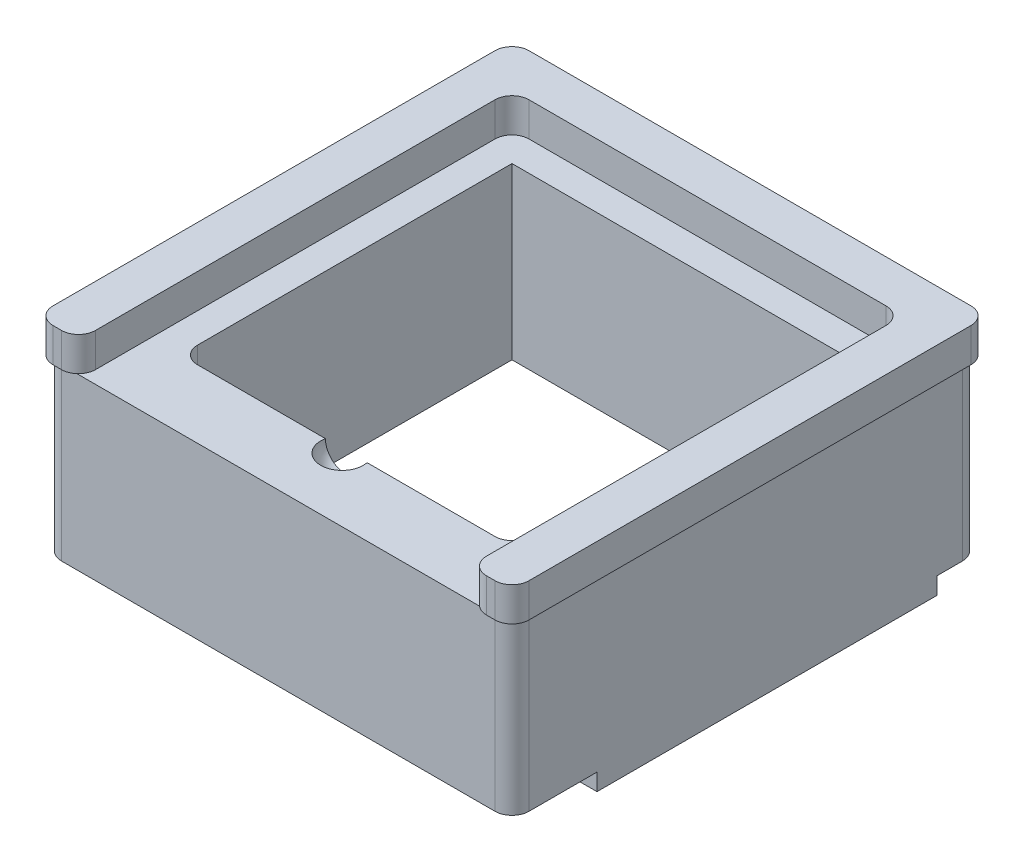
SolidWorks part; units mm, degrees
ref_plane "Front Plane" through (0, 0, 0) normal (0, 0, 1) x (1, 0, 0)
ref_plane "Top Plane" through (0, 0, 0) normal (0, 1, 0) x (1, 0, 0)
ref_plane "Right Plane" through (0, 0, 0) normal (1, 0, 0) x (0, 0, -1)
sketch "Sketch1" plane through (0, 0, 0) normal (0, 1, 0) x (1, 0, 0)
  line L1 (-14, -14) -> (14, -14)
  line L2 (-14, -14) -> (-14, 14)
  line L3 (-14, 14) -> (14, 14)
  line L4 (14, -14) -> (14, 14)
  line L5 (-14, -14) -> (14, 14) construction
  line L6 (-14, 14) -> (14, -14) construction
  line L7 (-11.5, -14) -> (11.5, -14)
  line L8 (-11.5, -14) -> (-11.5, 11.5)
  line L9 (-11.5, 11.5) -> (11.5, 11.5)
  line L10 (11.5, -14) -> (11.5, 11.5)
  point P0 (0, 0)
  point P13 (0, -14)
  point P14 (0, -14)
  dimension "D1" = 2.5
  dimension "D2" = 28
  dimension "D3" = 2.5
extrude "Boss-Extrude1" add sketch "Sketch1" along normal blind 2 contours L10 L1 L4 L3 L2 L8 L9 region at (-13.604, 0, 0)
sketch "Sketch3" plane through (0, 0, 0) normal (0, -1, 0) x (1, 0, 0)
  line L1 (-13.75, -13.75) -> (13.75, -13.75)
  line L2 (-13.75, -13.75) -> (-13.75, 13.75)
  line L3 (-13.75, 13.75) -> (13.75, 13.75)
  line L4 (13.75, -13.75) -> (13.75, 13.75)
  line L5 (-13.75, -13.75) -> (13.75, 13.75) construction
  line L6 (-13.75, 13.75) -> (13.75, -13.75) construction
  line L7 (-9.75, -9.75) -> (9.75, -9.75)
  line L8 (-9.75, -9.75) -> (-9.75, 9.75)
  line L9 (-9.75, 9.75) -> (9.75, 9.75)
  line L10 (9.75, -9.75) -> (9.75, 9.75)
  line L11 (-9.75, -9.75) -> (9.75, 9.75) construction
  line L12 (-9.75, 9.75) -> (9.75, -9.75) construction
  point P0 (0, 0)
  point P6 (0, 0)
  dimension "D1" = 27.5
  dimension "D2" = 4
extrude "Boss-Extrude2" add sketch "Sketch3" along normal blind 10 contours L2 L1 L4 L3 | L8 L7 L10 L9
sketch "Sketch4" plane through (0, -10, 0) normal (0, -1, 0) x (1, 0, 0)
  line L0 (0, -1000) -> (0, 49000) construction
  line L1 (-13.75, -11.25) -> (-12.75, -11.25)
  line L2 (-13.75, -11.25) -> (-13.75, 8.75)
  line L3 (-13.75, 8.75) -> (-12.75, 8.75)
  line L4 (-12.75, -11.25) -> (-12.75, 8.75)
  line L5 (12.75, -11.25) -> (12.75, 8.75)
  line L6 (13.75, 8.75) -> (12.75, 8.75)
  line L7 (13.75, -11.25) -> (13.75, 8.75)
  line L8 (13.75, -11.25) -> (12.75, -11.25)
  line L9 (-13.75, -13.75) -> (-13.75, 13.75) construction
  line L10 (-13.75, 13.75) -> (13.75, 13.75) construction
  dimension "D1" = 20
  dimension "D2" = 1
  dimension "D3" = 5
extrude "Boss-Extrude3" add sketch "Sketch4" along normal blind 1
sketch "Sketch5" plane through (0, 0, 0) normal (1, 0, 0) x (0, 0, -1)
  line L3 (-1000, 0) -> (49000, 0) construction
  circle A0 centre (-10, 0) radius 1.25
  point P0 (-11.5078, 0)
  dimension "D1" = 2.5
  dimension "D2" = 10
revolve "Cut-Revolve4" cut sketch "Sketch5" angle 360 about L3 region at (0, -0.5305, 10)
fillet "Fillet2" radius 1 14 edges at (-13.75, -5, 13.75) (13.75, -5, 13.75) (13.75, -5, -13.75) (-13.75, -5, -13.75) (-11.5, 1, -11.5) (-9.75, -5, 9.75) (9.75, -5, 9.75) (11.5, 1, -11.5) (-11.5, 1, 14) (14, 1, -14) (14, 1, 14) (11.5, 1, 14) (-14, 1, 14) (-14, 1, -14)
